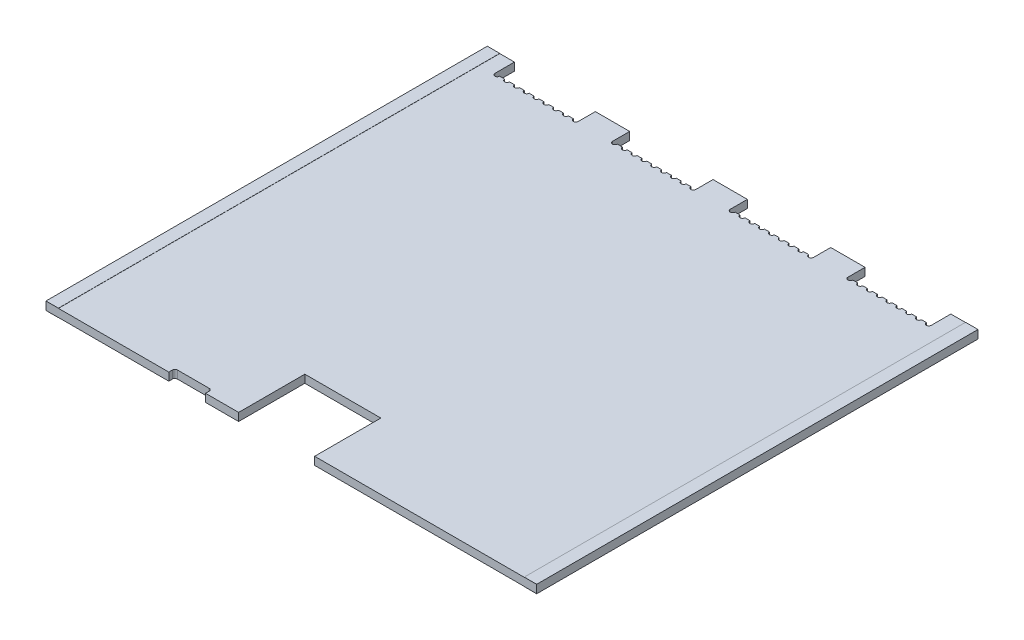
SolidWorks part; units mm, degrees
ref_plane "Front Plane" through (0, 0, 0) normal (0, 0, 1) x (1, 0, 0)
ref_plane "Top Plane" through (0, 0, 0) normal (0, 1, 0) x (1, 0, 0)
ref_plane "Right Plane" through (0, 0, 0) normal (1, 0, 0) x (0, 0, -1)
sketch "Sketch1" plane through (0, 0, 0) normal (0, 1, 0) x (1, 0, 0)
  line L0 (39.25, 0) -> (39.25, 13.5)
  line L1 (0, 90) -> (5.5, 90)
  line L2 (5.5, 90) -> (5.5, 86)
  line L3 (6.5, 86) -> (7.5, 86)
  line L4 (8.5, 86) -> (9.5, 86)
  line L5 (10.5, 86) -> (11.5, 86)
  line L6 (12.5, 86) -> (13.5, 86)
  line L7 (14.5, 86) -> (15.5, 86)
  line L8 (16.5, 86) -> (17.5, 86)
  line L9 (18.5, 86) -> (19.5, 86)
  line L10 (20.5, 86) -> (21.5, 86)
  line L11 (22.5, 86) -> (22.5, 89.5)
  line L12 (22.5, 89.5) -> (29.5, 89.5)
  line L13 (29.5, 89.5) -> (29.5, 86)
  line L14 (30.5, 86) -> (31.5, 86)
  line L15 (32.5, 86) -> (33.5, 86)
  line L16 (34.5, 86) -> (35.5, 86)
  line L17 (36.5, 86) -> (37.5, 86)
  line L18 (38.5, 86) -> (39.5, 86)
  line L19 (40.5, 86) -> (41.5, 86)
  line L20 (42.5, 86) -> (43.5, 86)
  line L21 (44.5, 86) -> (45.5, 86)
  line L22 (46.5, 86) -> (46.5, 89.5)
  line L23 (46.5, 89.5) -> (53.5, 89.5)
  line L24 (53.5, 89.5) -> (53.5, 86)
  line L25 (54.5, 86) -> (55.5, 86)
  line L26 (56.5, 86) -> (57.5, 86)
  line L27 (58.5, 86) -> (59.5, 86)
  line L28 (60.5, 86) -> (61.5, 86)
  line L29 (62.5, 86) -> (63.5, 86)
  line L30 (64.5, 86) -> (65.5, 86)
  line L31 (66.5, 86) -> (67.5, 86)
  line L32 (68.5, 86) -> (69.5, 86)
  line L33 (70.5, 86) -> (70.5, 89.5)
  line L34 (70.5, 89.5) -> (77.5, 89.5)
  line L35 (77.5, 89.5) -> (77.5, 86)
  line L36 (78.5, 86) -> (79.5, 86)
  line L37 (80.5, 86) -> (81.5, 86)
  line L38 (82.5, 86) -> (83.5, 86)
  line L39 (84.5, 86) -> (85.5, 86)
  line L40 (86.5, 86) -> (87.5, 86)
  line L41 (88.5, 86) -> (89.5, 86)
  line L42 (90.5, 86) -> (91.5, 86)
  line L43 (92.5, 86) -> (93.5, 86)
  line L44 (94.5, 86) -> (94.5, 90)
  line L45 (94.5, 90) -> (100, 90)
  line L46 (100, 90) -> (100, 0)
  line L47 (100, 0) -> (54.75, 0)
  line L48 (32.5, 0) -> (32.5, 0.75)
  line L49 (32, 1.25) -> (25.5, 1.25)
  line L50 (25, 0.75) -> (25, 0)
  line L51 (25, 0) -> (13.5, 0)
  line L52 (39.25, 13.5) -> (54.75, 13.5)
  line L53 (54.75, 13.5) -> (54.75, 0)
  line L54 (32.5, 0) -> (39.25, 0)
  line L55 (13.5, 0) -> (0, 0)
  line L56 (0, 0) -> (0, 90)
  arc A0 (5.5, 86) -> (6.5, 86) centre (6, 86) ccw
  arc A1 (7.5, 86) -> (8.5, 86) centre (8, 86) ccw
  arc A2 (9.5, 86) -> (10.5, 86) centre (10, 86) ccw
  arc A3 (11.5, 86) -> (12.5, 86) centre (12, 86) ccw
  arc A4 (13.5, 86) -> (14.5, 86) centre (14, 86) ccw
  arc A5 (15.5, 86) -> (16.5, 86) centre (16, 86) ccw
  arc A6 (17.5, 86) -> (18.5, 86) centre (18, 86) ccw
  arc A7 (19.5, 86) -> (20.5, 86) centre (20, 86) ccw
  arc A8 (21.5, 86) -> (22.5, 86) centre (22, 86) ccw
  arc A9 (29.5, 86) -> (30.5, 86) centre (30, 86) ccw
  arc A10 (31.5, 86) -> (32.5, 86) centre (32, 86) ccw
  arc A11 (33.5, 86) -> (34.5, 86) centre (34, 86) ccw
  arc A12 (35.5, 86) -> (36.5, 86) centre (36, 86) ccw
  arc A13 (37.5, 86) -> (38.5, 86) centre (38, 86) ccw
  arc A14 (39.5, 86) -> (40.5, 86) centre (40, 86) ccw
  arc A15 (41.5, 86) -> (42.5, 86) centre (42, 86) ccw
  arc A16 (43.5, 86) -> (44.5, 86) centre (44, 86) ccw
  arc A17 (45.5, 86) -> (46.5, 86) centre (46, 86) ccw
  arc A18 (53.5, 86) -> (54.5, 86) centre (54, 86) ccw
  arc A19 (55.5, 86) -> (56.5, 86) centre (56, 86) ccw
  arc A20 (57.5, 86) -> (58.5, 86) centre (58, 86) ccw
  arc A21 (59.5, 86) -> (60.5, 86) centre (60, 86) ccw
  arc A22 (61.5, 86) -> (62.5, 86) centre (62, 86) ccw
  arc A23 (63.5, 86) -> (64.5, 86) centre (64, 86) ccw
  arc A24 (65.5, 86) -> (66.5, 86) centre (66, 86) ccw
  arc A25 (67.5, 86) -> (68.5, 86) centre (68, 86) ccw
  arc A26 (69.5, 86) -> (70.5, 86) centre (70, 86) ccw
  arc A27 (77.5, 86) -> (78.5, 86) centre (78, 86) ccw
  arc A28 (79.5, 86) -> (80.5, 86) centre (80, 86) ccw
  arc A29 (81.5, 86) -> (82.5, 86) centre (82, 86) ccw
  arc A30 (83.5, 86) -> (84.5, 86) centre (84, 86) ccw
  arc A31 (85.5, 86) -> (86.5, 86) centre (86, 86) ccw
  arc A32 (87.5, 86) -> (88.5, 86) centre (88, 86) ccw
  arc A33 (89.5, 86) -> (90.5, 86) centre (90, 86) ccw
  arc A34 (91.5, 86) -> (92.5, 86) centre (92, 86) ccw
  arc A35 (93.5, 86) -> (94.5, 86) centre (94, 86) ccw
  arc A36 (32.5, 0.75) -> (32, 1.25) centre (32, 0.75) ccw
  arc A37 (25.5, 1.25) -> (25, 0.75) centre (25.5, 0.75) ccw
extrude "FR4" add sketch "Sketch1" along normal blind 1.6154
sketch "Sketch2" plane through (0, 0, 0) normal (0, 0, 1) x (1, 0, 0)
  line L0 (0, 1.6154) -> (25, 1.6154) construction
  line L1 (2.5, 1.6154) -> (2.5, 1.651)
  line L2 (2.5, 1.651) -> (-0.0356, 1.651)
  line L3 (-0.0356, 1.651) -> (-0.0356, -0.0356)
  line L4 (-0.0356, -0.0356) -> (2.5, -0.0356)
  line L5 (2.5, -0.0356) -> (2.5, 0)
  line L6 (0, 0) -> (25, 0) construction
  line L7 (2.5, 0) -> (0, 0)
  line L8 (0, 0) -> (0, 1.6154)
  line L9 (0, 1.6154) -> (2.5, 1.6154)
  line L10 (-0.0356, 0.9975) -> (0, 0.9975) construction
  line L11 (100, 1.6154) -> (100, 0)
  line L12 (100.0356, -0.0356) -> (100.0356, 1.651)
  line L13 (100.0356, 0.6179) -> (100, 0.6179) construction
  line L14 (97.5, -0.0356) -> (100.0356, -0.0356)
  line L15 (100, 0) -> (97.5, 0)
  line L16 (100.0356, 1.651) -> (97.5, 1.651)
  line L17 (97.5, 1.6154) -> (100, 1.6154)
  line L18 (97.5, 0) -> (97.5, -0.0356)
  line L19 (97.5, 1.651) -> (97.5, 1.6154)
extrude "gold-plating" add sketch "Sketch2" against normal through all separate body
